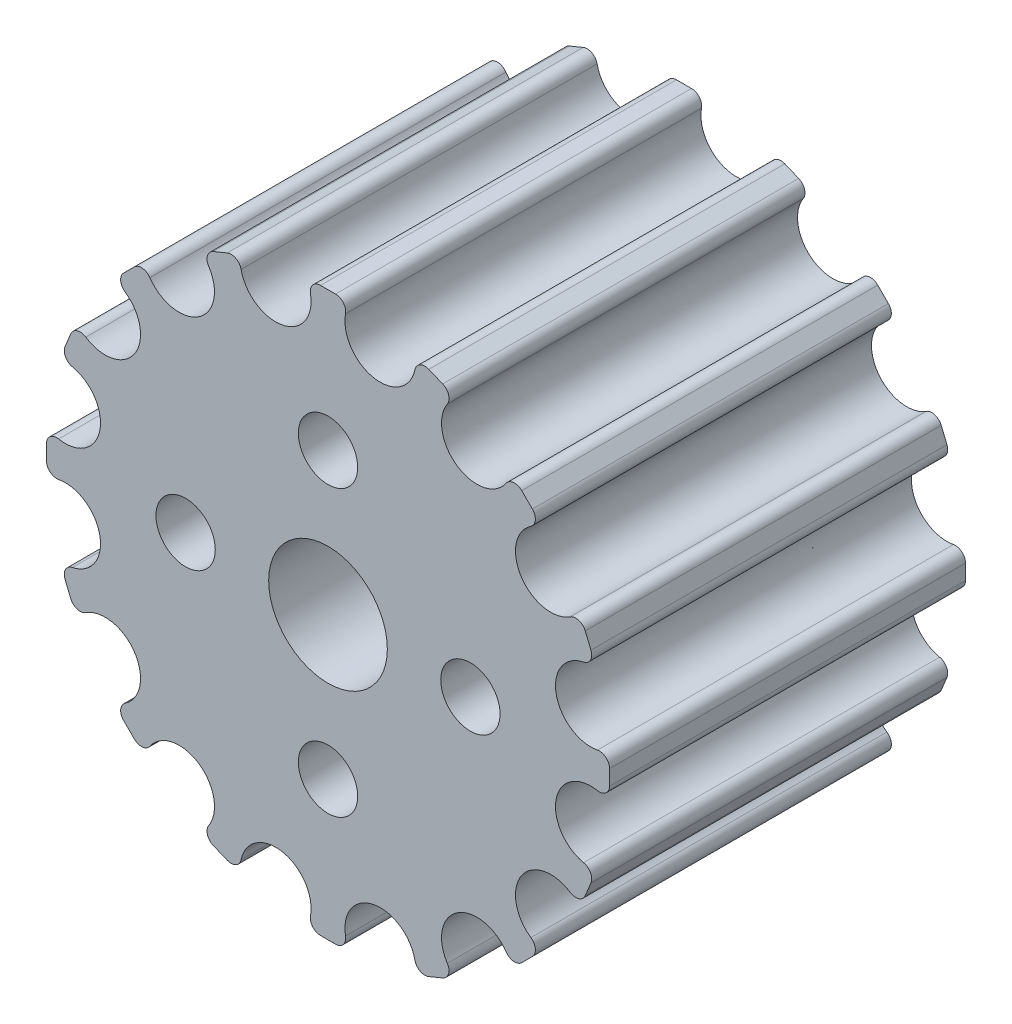
SolidWorks part; units mm, degrees
material "PE High Density"
ref_plane "Front Plane" through (0, 0, 0) normal (0, 0, 1) x (1, 0, 0)
ref_plane "Top Plane" through (0, 0, 0) normal (0, 1, 0) x (1, 0, 0)
ref_plane "Right Plane" through (0, 0, 0) normal (1, 0, 0) x (0, 0, -1)
sketch "Sketch2" plane through (0, 0, 0) normal (0, 0, 1) x (1, 0, 0)
  circle A0 centre (0, 0) radius 12.7324
  dimension "D1" = 25.4648
extrude "PD" add sketch "Sketch2" along normal mid plane 15
sketch "Sketch3" plane through (0, 0, 7.5) normal (0, 0, 1) x (1, 0, 0)
  line L0 (0, 0) -> (0, 11.8624) construction
  line L1 (0, 0) -> (2.203, 11.0754) construction
  line L2 (0, 11.8624) -> (0.3165, 11.8624)
  line L3 (0, 11.8624) -> (0, 12.7324)
  line L4 (4.5395, 10.9594) -> (4.8725, 11.7632)
  line L5 (4.5395, 10.9594) -> (4.2471, 11.0805)
  line L6 (2.203, 11.0754) -> (2.484, 12.4877) construction
  arc A0 (0.3165, 11.8624) -> (0.739, 11.3524) centre (0.3165, 11.4324) cw
  arc A1 (0.739, 11.3524) -> (3.6616, 10.7711) centre (2.203, 11.0754) ccw
  circle A2 centre (0, 0) radius 12.7324 construction
  arc A3 (0, 12.7324) -> (4.8725, 11.7632) centre (0, 0) cw
  arc A4 (4.2471, 11.0805) -> (3.6616, 10.7711) centre (4.0826, 10.6833) ccw
  point P8 (1.9124, 9.614)
  dimension "D1" = 0.43
  dimension "D2" = 1.49
  dimension "D3" = 0.87
  dimension "D4" = 11.25
  dimension "D5" = 2.93
extrude "Teeth" cut sketch "Sketch3" against normal up to surface (15 mm away) up to face at (12.7324, 0, -7.5)
pattern_circular "CirPattern1" count 16 over 360 about axis through (0, 0, 7.5) along (0, 0, 1) of "Teeth"
sketch "Sketch6" plane through (0, 0, 0) normal (0, 0, 1) x (1, 0, 0)
  circle A0 centre (0, 0) radius 5
extrude "Cut-Extrude2" [suppressed] cut sketch "Sketch6" against normal through all both and the other way through all
sketch "Sketch7" plane through (0, 0, -7.5) normal (0, 0, -1) x (-1, 0, 0)
  circle A0 centre (0, 6) radius 1.25
  circle A2 centre (6, 0) radius 1.25
  circle A3 centre (0, -6) radius 1.25
  circle A4 centre (-6, 0) radius 1.25
  point P12 (0, 0)
  dimension "D1" = 6
  dimension "D2" = 4
extrude "Cut-Extrude3" cut sketch "Sketch7" against normal blind 21
sketch "Sketch8" plane through (0, 0, -7.5) normal (0, 0, -1) x (-1, 0, 0)
  circle A0 centre (0, 0) radius 2.5
extrude "Cut-Extrude4" cut sketch "Sketch8" against normal blind 25
equation "\"D1@Sketch4\"= 16 + 2"
equation "\"D1\" = 16"
equation "\"D4@Sketch3\" = 180 / 16"
equation "\"D1@Sketch2\" = 16 * 5 / pi"
